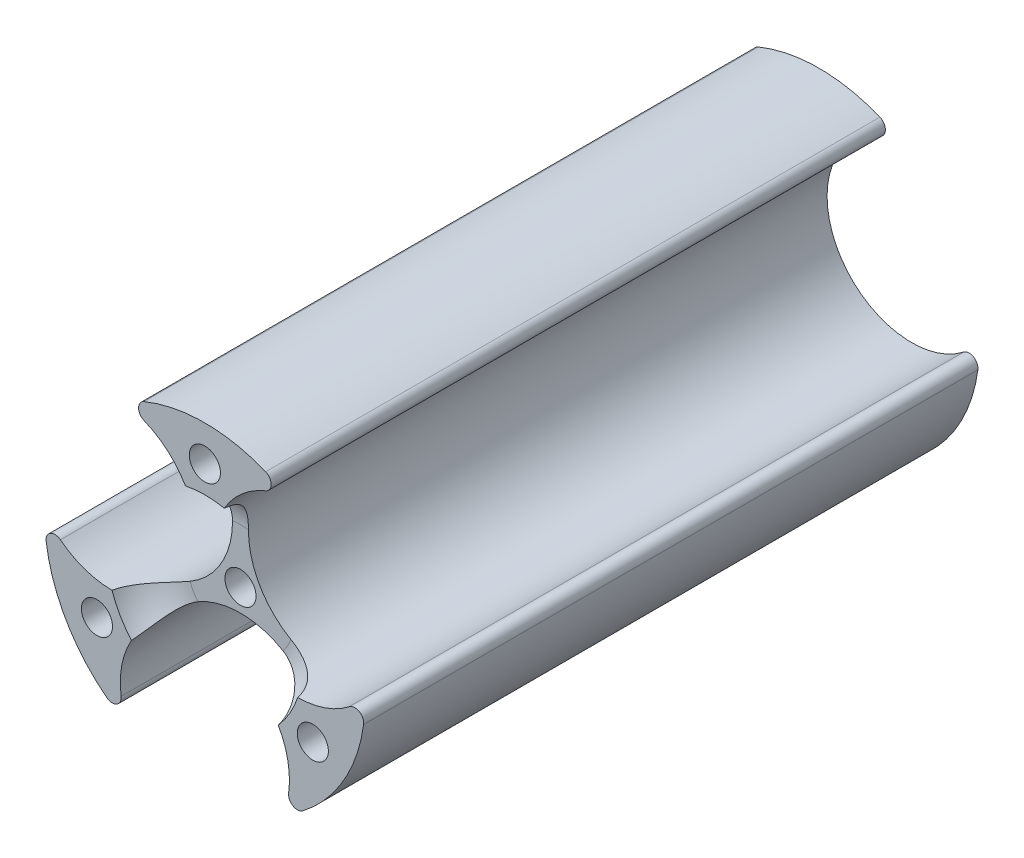
SolidWorks part; units mm, degrees
material "ABS"
ref_plane "Спереди" through (0, 0, 0) normal (0, 0, 1) x (1, 0, 0)
ref_plane "Сверху" through (0, 0, 0) normal (0, 1, 0) x (1, 0, 0)
ref_plane "Справа" through (0, 0, 0) normal (1, 0, 0) x (0, 0, -1)
sketch "Эскиз1" plane through (0, 0, 0) normal (0, 0, 1) x (1, 0, 0)
  line L0 (0, 0) -> (0, -18) construction
  line L1 (0, 0) -> (0, 18) construction
  circle A0 centre (0, 0) radius 18
  circle A1 centre (0, -12) radius 9.5
  circle A2 centre (-10.3923, 6) radius 9.5
  circle A3 centre (10.3923, 6) radius 9.5
  circle A4 centre (0, 14) radius 1.75
  circle A5 centre (12.1244, -7) radius 1.75
  circle A6 centre (-12.1244, -7) radius 1.75
  circle A7 centre (0, 0) radius 1.75
  point P13 (0, 0)
  point P20 (0, 0)
  dimension "D1" = 19
  dimension "D4" = 36
  dimension "D5" = 3.5
  dimension "D7" = 3.5
  dimension "D2" = 12
  dimension "D6" = 14
  dimension "D3" = 3
extrude "Бобышка-Вытянуть1" add sketch "Эскиз1" along normal blind 65 contours A3 A0 A2 A1 region at (15.086, -8.8822, 0)
fillet "Скругление1" radius 1 6 edges at (17.9974, 0.3068, 32.5) (8.733, -15.7396, 32.5) (-8.733, -15.7396, 32.5) (-17.9974, 0.3068, 32.5) (-9.2644, 15.4328, 32.5) (9.2644, 15.4328, 32.5)
sketch "Эскиз2" plane through (0, 0, 65) normal (0, 0, 1) x (1, 0, 0)
  arc A0 (6.8256, 16.6557) -> (-6.8256, 16.6557) centre (0, 0) ccw
  circle A1 centre (0, 14) radius 1.75
  circle A2 centre (0, 14) radius 1.75
  circle A3 centre (10.3923, 6) radius 9.5
  arc A4 (6.8222, 14.8037) -> (16.2314, -1.4936) centre (10.3923, 6) ccw
  circle A5 centre (-10.3923, 6) radius 9.5
  arc A6 (-16.2314, -1.4936) -> (-6.8222, 14.8037) centre (-10.3923, 6) ccw
  circle A7 centre (0, -12) radius 9.5
  arc A8 (9.4092, -13.31) -> (-9.4092, -13.31) centre (0, -12) ccw
  circle A9 centre (0, 0) radius 18
  arc A10 (-17.837, -2.4167) -> (-11.0114, -14.239) centre (0, 0) ccw
  circle A11 centre (0, 0) radius 1.75
  arc A12 (11.0114, -14.239) -> (17.837, -2.4167) centre (0, 0) ccw
  arc A13 (17.837, -2.4167) -> (16.2314, -1.4936) centre (16.8461, -2.2824) ccw
  arc A14 (6.8222, 14.8037) -> (16.2314, -1.4936) centre (10.3923, 6) ccw
  arc A15 (6.8222, 14.8037) -> (6.8256, 16.6557) centre (6.4464, 15.7304) ccw
  arc A16 (6.8256, 16.6557) -> (-6.8256, 16.6557) centre (0, 0) ccw
  arc A17 (-6.8256, 16.6557) -> (-6.8222, 14.8037) centre (-6.4464, 15.7304) ccw
  arc A18 (-16.2314, -1.4936) -> (-6.8222, 14.8037) centre (-10.3923, 6) ccw
  arc A19 (-16.2314, -1.4936) -> (-17.837, -2.4167) centre (-16.8461, -2.2824) ccw
  arc A20 (-17.837, -2.4167) -> (-11.0114, -14.239) centre (0, 0) ccw
  arc A21 (-11.0114, -14.239) -> (-9.4092, -13.31) centre (-10.3997, -13.4479) ccw
  arc A22 (9.4092, -13.31) -> (-9.4092, -13.31) centre (0, -12) ccw
  arc A23 (9.4092, -13.31) -> (11.0114, -14.239) centre (10.3997, -13.4479) ccw
  arc A24 (11.0114, -14.239) -> (17.837, -2.4167) centre (0, 0) ccw
  arc A25 (17.837, -2.4167) -> (16.2314, -1.4936) centre (16.8461, -2.2824) ccw
  arc A26 (6.8222, 14.8037) -> (16.2314, -1.4936) centre (10.3923, 6) ccw
  arc A27 (6.8222, 14.8037) -> (6.8256, 16.6557) centre (6.4464, 15.7304) ccw
  arc A28 (6.8256, 16.6557) -> (-6.8256, 16.6557) centre (0, 0) ccw
  arc A29 (-6.8256, 16.6557) -> (-6.8222, 14.8037) centre (-6.4464, 15.7304) ccw
  arc A30 (-16.2314, -1.4936) -> (-6.8222, 14.8037) centre (-10.3923, 6) ccw
  arc A31 (-16.2314, -1.4936) -> (-17.837, -2.4167) centre (-16.8461, -2.2824) ccw
  arc A32 (-17.837, -2.4167) -> (-11.0114, -14.239) centre (0, 0) ccw
  arc A33 (-11.0114, -14.239) -> (-9.4092, -13.31) centre (-10.3997, -13.4479) ccw
  arc A34 (9.4092, -13.31) -> (-9.4092, -13.31) centre (0, -12) ccw
  arc A35 (9.4092, -13.31) -> (11.0114, -14.239) centre (10.3997, -13.4479) ccw
  circle A36 centre (0, 0) radius 1.75
  circle A37 centre (-12.1244, -7) radius 1.75
  circle A38 centre (-12.1244, -7) radius 1.75
  circle A39 centre (12.1244, -7) radius 1.75
  circle A40 centre (12.1244, -7) radius 1.75
  arc A41 (11.0114, -14.239) -> (17.837, -2.4167) centre (0, 0) ccw
  circle A42 centre (0, 0) radius 11
  circle M23 centre (-12.1244, -7) radius 1.75
  circle M24 centre (12.1244, -7) radius 1.75
  circle M25 centre (0, 14) radius 1.75
  arc M26 (11.0114, -14.239) -> (17.837, -2.4167) centre (0, 0) ccw
  arc M27 (17.837, -2.4167) -> (16.2314, -1.4936) centre (16.8461, -2.2824) ccw
  arc M28 (16.2314, -1.4936) -> (6.8222, 14.8037) centre (10.3923, 6) cw
  arc M29 (6.8222, 14.8037) -> (6.8256, 16.6557) centre (6.4464, 15.7304) ccw
  arc M30 (6.8256, 16.6557) -> (-6.8256, 16.6557) centre (0, 0) ccw
  arc M31 (-6.8256, 16.6557) -> (-6.8222, 14.8037) centre (-6.4464, 15.7304) ccw
  arc M32 (-6.8222, 14.8037) -> (-16.2314, -1.4936) centre (-10.3923, 6) cw
  arc M33 (-16.2314, -1.4936) -> (-17.837, -2.4167) centre (-16.8461, -2.2824) ccw
  arc M34 (-17.837, -2.4167) -> (-11.0114, -14.239) centre (0, 0) ccw
  arc M35 (-11.0114, -14.239) -> (-9.4092, -13.31) centre (-10.3997, -13.4479) ccw
  arc M36 (-9.4092, -13.31) -> (9.4092, -13.31) centre (0, -12) cw
  arc M37 (9.4092, -13.31) -> (11.0114, -14.239) centre (10.3997, -13.4479) ccw
  dimension "D10" = 22
  dimension "D1" = 0
  dimension "D2" = 0
  dimension "D3" = 0
  dimension "D4" = 0
  dimension "D5" = 0
  dimension "D6" = 0
  dimension "D7" = 0
  dimension "D8" = 0
  dimension "D9" = 0
extrude "Бобышка-Вытянуть2" add sketch "Эскиз2" along normal blind 4 contours A42 M28 M29 M30 M31 M32 M25 | A42 M36 M37 M26 M27 M28 M24 | A42 M32 M33 M34 M35 M36 M23 region at (7.2809, 15.7288, 65) region at (17.2633, -1.5568, 65) region at (-13.5497, -3.1325, 65)
fillet "Скругление2" radius 5 3 edges at (-9.5263, -5.5, 65) (9.5263, -5.5, 65) (0, 11, 65)
